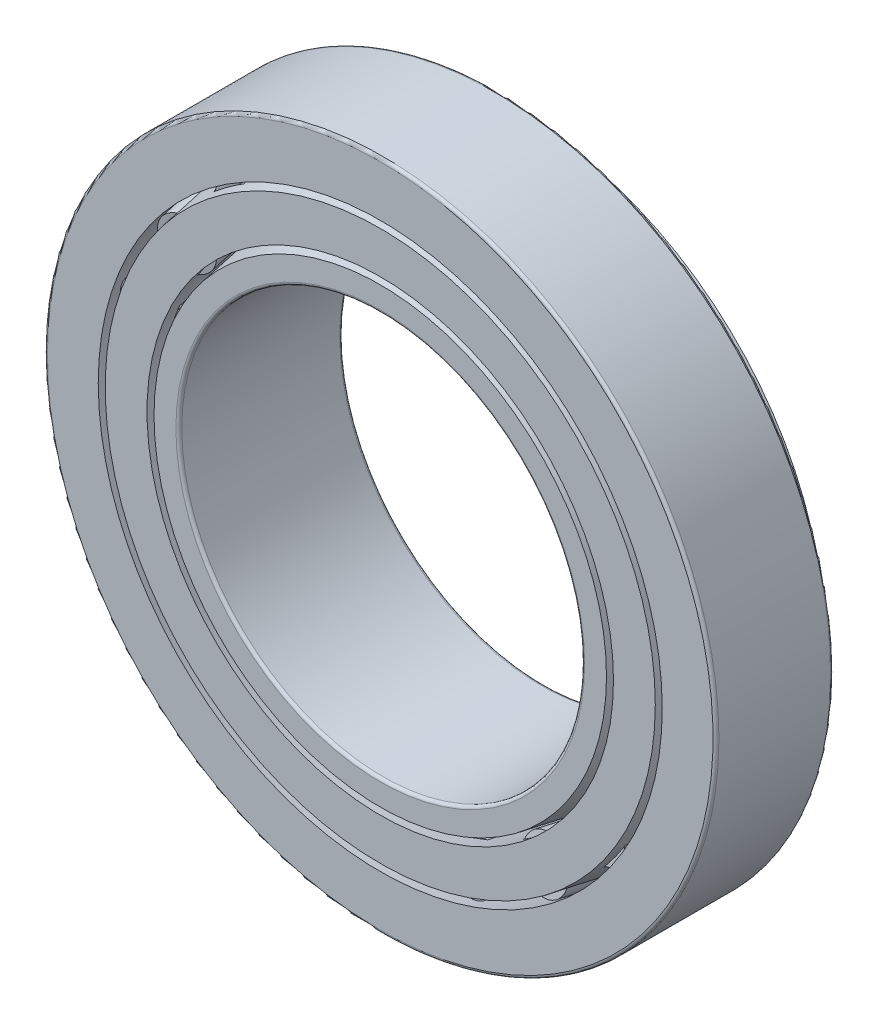
SolidWorks part; units mm, degrees
ref_plane "Front Plane" through (0, 0, 0) normal (0, 0, 1) x (1, 0, 0)
ref_plane "Top Plane" through (0, 0, 0) normal (0, 1, 0) x (1, 0, 0)
ref_plane "Right Plane" through (0, 0, 0) normal (1, 0, 0) x (0, 0, -1)
sketch "Sketch1" plane through (0, 0, 0) normal (1, 0, 0) x (0, 0, -1)
  line L0 (-15.5003, 0) -> (15.5003, 0) construction
  line L1 (0, 0) -> (0, 63.5) construction
  line L2 (-15.5004, 38.1) -> (15.5004, 38.1) construction
  line L3 (15.5004, 38.1) -> (15.5004, 48.26) construction
  line L4 (15.5004, 48.26) -> (-15.5004, 42.7937) construction
  line L5 (-15.5004, 42.7937) -> (-15.5004, 38.1) construction
  line L7 (-15.5004, 63.5) -> (6.7246, 63.5)
  line L8 (6.7246, 63.5) -> (6.7246, 57.2589)
  line L9 (6.7246, 57.2589) -> (-15.5004, 53.34)
  line L10 (-15.5004, 53.34) -> (-15.5004, 63.5)
  line L11 (-15.5004, 53.34) -> (-13.6968, 43.1117) construction
  line L12 (11.4108, 58.0852) -> (13.2143, 47.8569) construction
  line L14 (-15.5004, 42.7937) -> (-13.6968, 43.1117) construction
  line L15 (-15.5004, 42.7937) -> (13.2143, 47.8569) construction
  point P5 (0, 38.1)
  dimension "D1" = 100
  dimension "Width" = 31.0007
  dimension "OD" = 127
  dimension "Shaft Dia" = 76.2
  dimension "D2" = 25.4
  dimension "D3" = 10.16
  dimension "Outer Wd" = 22.225
  dimension "Bearing Wd" = 28.7147
revolve "Revolve1" add sketch "Sketch1" angle 360 about L0
sketch "Sketch5" plane through (0, 0, 0) normal (1, 0, 0) x (0, 0, -1)
  line L0 (15.5004, 48.26) -> (-15.5004, 42.7937) construction
  line L1 (15.5004, 48.26) -> (-15.5004, 42.7937)
  line L2 (-15.5004, 42.7937) -> (-15.5004, 38.1)
  line L3 (-15.5004, 38.1) -> (15.5004, 38.1)
  line L4 (15.5004, 38.1) -> (15.5004, 48.26)
revolve "Revolve4" add sketch "Sketch5" angle 360 about L0
sketch "Sketch2" plane through (0, 0, 0) normal (1, 0, 0) x (0, 0, -1)
  line L0 (-15.5004, 52.0217) -> (-15.5004, 44.112)
  line L1 (6.7246, 55.9406) -> (11.6363, 56.8066)
  line L2 (-15.5004, 44.112) -> (6.7246, 48.0309)
  line L3 (11.4108, 58.0852) -> (13.2143, 47.8569) construction
  line L4 (6.7246, 48.0309) -> (6.7246, 55.9406) construction
  line L5 (6.7246, 55.9406) -> (-15.5004, 52.0217)
  line L6 (6.7246, 57.2589) -> (-15.5004, 53.34) construction
  line L7 (15.5004, 48.26) -> (-15.5004, 42.7937) construction
  line L8 (-15.5004, 53.34) -> (6.7246, 57.2589) construction
  line L9 (-15.5004, 42.7937) -> (13.2143, 47.8569) construction
  line L10 (11.6363, 56.8066) -> (12.9889, 49.1354)
  line L11 (-15.5004, 53.34) -> (-15.5004, 52.0217) construction
  line L12 (-15.5004, 44.112) -> (-15.5004, 42.7937) construction
  line L13 (6.7246, 63.5) -> (6.7246, 57.2589) construction
  line L14 (12.9889, 49.1354) -> (6.7246, 48.0309)
  dimension "D1" = 10.386
  dimension "D2" = 7.7895
revolve "Revolve2" add sketch "Sketch2" angle 360 about L0
sketch "Sketch3" plane through (0, 0, 0) normal (1, 0, 0) x (0, 0, -1)
  line L0 (-15.5004, 48.0669) -> (6.7246, 51.9857) construction
  line L1 (-15.5004, 52.0217) -> (-15.5004, 44.112) construction
  line L2 (6.7246, 48.0309) -> (6.7246, 55.9406) construction
  line L3 (-12.7951, 48.5439) -> (-13.6968, 53.658)
  line L5 (-13.6968, 53.658) -> (5.8229, 57.0999)
  line L6 (5.8229, 57.0999) -> (6.7246, 51.9857)
  line L7 (6.7246, 51.9857) -> (-12.7951, 48.5439)
  line L8 (6.7246, 57.2589) -> (-15.5004, 53.34) construction
  line L9 (-15.5004, 48.0669) -> (-14.5986, 48.2259) construction
  line L10 (-15.5004, 53.34) -> (-13.6968, 43.1117) construction
  line L11 (-14.5986, 48.2259) -> (-13.6968, 48.3849) construction
  line L12 (-13.6968, 48.3849) -> (-12.7951, 48.5439) construction
revolve "Cut-Revolve1" cut sketch "Sketch3" angle 360 about L0
sketch "Sketch4" plane through (0, 0, 0) normal (1, 0, 0) x (0, 0, -1)
  line L0 (-13.6527, 53.4079) -> (5.867, 56.8497)
  line L1 (5.867, 56.8497) -> (6.7246, 51.9857)
  line L2 (6.7246, 51.9857) -> (-12.7951, 48.5439)
  line L3 (-15.5004, 48.0669) -> (-12.7951, 48.5439) construction
  line L4 (-12.7951, 48.5439) -> (-13.6527, 53.4079)
  line L6 (6.7246, 51.9857) -> (-12.7951, 48.5439) construction
  line L7 (6.7246, 57.2589) -> (-15.5004, 53.34) construction
  dimension "D1" = 0.254
revolve "Revolve3" add sketch "Sketch4" angle 360 about L0
ref_axis "Axis1" through (0, 0, -15.5003) along (0, 0, 1)
pattern_circular "CirPattern1" count 20 over 360 about axis through (0, 0, -15.5003) along (0, 0, 1) of "Cut-Revolve1"
pattern_circular "CirPattern2" count 20 over 360 about axis through (0, 0, -15.5003) along (0, 0, 1) of bodies 403
fillet "Fillet1" radius 0.5556 2 edges at (63.5, 0, -6.7246) (63.5, 0, 15.5004)
fillet "Fillet2" radius 0.5556 2 edges at (38.1, 0, -15.5004) (38.1, 0, 15.5004)
sketch "Sketch6" plane through (0, 0, 0) normal (1, 0, 0) x (0, 0, -1)
  line L0 (-88.5254, 63.5) -> (-88.5254, 53.34)
  line L1 (-88.5254, 53.34) -> (-66.3004, 57.2589)
  line L2 (-66.3004, 57.2589) -> (-66.3004, 63.5)
  line L3 (-66.3004, 63.5) -> (-88.5254, 63.5)
  line L4 (-15.5004, 63.5) -> (6.7246, 63.5) construction
  line L5 (-15.5004, 53.34) -> (-15.5004, 63.5) construction
  line L6 (6.7246, 63.5) -> (6.7246, 57.2589) construction
  dimension "Ring Separation" = 50.8
revolve "Revolve5" [suppressed] add sketch "Sketch6" angle 360 about L0
fillet "Fillet3" [suppressed] radius 0.5556
delete or keep bodies "Body-Delete1" [suppressed] type delete bodies bodies 399
sketch "Sketch8" plane through (0, 0, 0) normal (0, 0, 1) x (1, 0, 0)
  line L0 (0, 79.375) -> (0, -79.375) construction
  dimension "D1" = 158.75
equation "\"D3@Sketch1\" = \"D2@Sketch1\"/2.5"
equation "\"D2@Sketch2\" = \"D1@Sketch2\"*.75"
equation "\"D1@Fillet1\" = \"Outer Wd@Sketch1\"*.025"
equation "\"D1@Fillet2\" = \"D1@Fillet1\""
equation "\"D1@Fillet3\" = \"D1@Fillet1\""
equation "\"Rollers@CirPattern2\" = \"D1@CirPattern1\""
equation "\"D1@Sketch8\" = \"OD@Sketch1\"*1.250"
